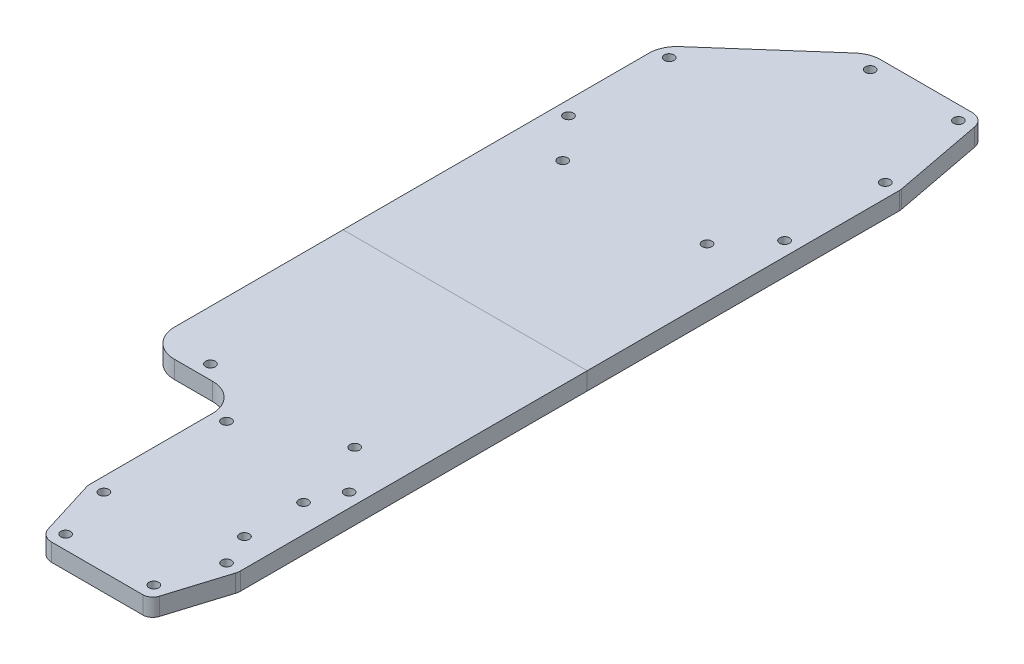
SolidWorks part; units mm, degrees
ref_plane "Front Plane" through (0, 0, 0) normal (0, 0, 1) x (1, 0, 0)
ref_plane "Top Plane" through (0, 0, 0) normal (0, 1, 0) x (1, 0, 0)
ref_plane "Right Plane" through (0, 0, 0) normal (1, 0, 0) x (0, 0, -1)
sketch "Sketch1" plane through (0, 0, 0) normal (0, 1, 0) x (1, 0, 0)
  line L0 (45, 295) -> (76.8, 295) construction
  line L1 (0, 0) -> (88, 0)
  line L2 (0, 0) -> (0, 300)
  line L3 (0, 300) -> (88, 300)
  line L4 (88, 0) -> (88, 300)
  line L5 (18, 211.2) -> (70, 211.2) construction
  line L6 (18, 211.2) -> (18, 84.2) construction
  line L7 (18, 84.2) -> (70, 84.2) construction
  line L8 (70, 211.2) -> (70, 84.2) construction
  line L9 (38.8, 69.2) -> (83, 69.2) construction
  line L10 (38.8, 69.2) -> (38.8, 25) construction
  line L11 (38.8, 25) -> (83, 25) construction
  line L12 (83, 69.2) -> (83, 25) construction
  line L13 (5.05, 226.2) -> (82.95, 226.2) construction
  line L14 (5.05, 226.2) -> (5.05, 262.5) construction
  line L15 (5.05, 262.5) -> (82.95, 262.5) construction
  line L16 (82.95, 226.2) -> (82.95, 262.5) construction
  line L17 (45, 5) -> (76.8, 5) construction
  line L18 (38.8, 25) -> (45, 5) construction
  line L19 (76.8, 5) -> (83, 25) construction
  line L20 (34.0242, 23.5195) -> (40.2242, 3.5195)
  line L21 (40, 300) -> (0, 264.7822)
  line L22 (87.7758, 23.5195) -> (81.2684, 2.5279)
  line L23 (78, 57.75) -> (78, 36.45) construction
  line L24 (5.05, 262.5) -> (0, 262.5) construction
  line L25 (5.05, 262.5) -> (1.7129, 266.2903) construction
  line L26 (78, 36.45) -> (83, 25) construction
  line L27 (78, 57.75) -> (83, 69.2) construction
  line L28 (81.7114, 295.9371) -> (87.9105, 263.4465)
  line L29 (33.8, 79.2) -> (0, 79.2)
  line L30 (33.8, 25) -> (33.8, 79.2)
  circle A0 centre (18, 211.2) radius 1.75
  circle A1 centre (70, 84.2) radius 1.75
  circle A2 centre (18, 84.2) radius 1.75
  circle A3 centre (70, 211.2) radius 1.75
  circle A4 centre (5.05, 262.5) radius 1.75
  circle A5 centre (5.05, 226.2) radius 1.75
  circle A6 centre (82.95, 226.2) radius 1.75
  circle A7 centre (82.95, 262.5) radius 1.75
  circle A8 centre (38.8, 69.2) radius 1.75
  circle A9 centre (83, 69.2) radius 1.75
  circle A10 centre (83, 25) radius 1.75
  circle A11 centre (38.8, 25) radius 1.75
  circle A12 centre (45, 295) radius 1.75
  circle A13 centre (76.8, 295) radius 1.75
  circle A14 centre (45, 5) radius 1.75
  circle A15 centre (76.8, 5) radius 1.75
  arc A16 (88, 25) -> (87.7758, 23.5195) centre (83, 25) cw
  arc A17 (77.8382, 0) -> (81.2684, 2.5279) centre (77.8382, 3.5912) ccw
  arc A18 (40.2242, 3.5195) -> (45, 0) centre (45, 5) ccw
  circle A19 centre (78, 57.75) radius 1.75
  circle A20 centre (78, 36.45) radius 1.75
  arc A21 (76.8, 300) -> (81.7114, 295.9371) centre (76.8, 295) cw
  arc A22 (87.9105, 263.4465) -> (88, 262.5) centre (82.95, 262.5) cw
  arc A23 (34.0242, 23.5195) -> (33.8, 25) centre (38.8, 25) cw
  point P61 (16.4478, 79.2)
  point P62 (34.0877, 79.2)
  dimension "D3" = 3.5
  dimension "D14" = 3.5
  dimension "D2" = 300
  dimension "D4" = 52
  dimension "D5" = 127
  dimension "D6" = 18
  dimension "D7" = 77.9
  dimension "D8" = 36.3
  dimension "D9" = 44.2
  dimension "D11" = 5.05
  dimension "D12" = 15
  dimension "D13" = 15
  dimension "D10" = 5
  dimension "D15" = 5
  dimension "D16" = 11.2
  dimension "D18" = 5
  dimension "D17" = 31.8
  dimension "D20" = 20
  dimension "D25" = 5
  dimension "D21" = 21.3
  dimension "D22" = 5
  dimension "D19" = 5
  dimension "D23" = 88
extrude "Boss-Extrude1" add sketch "Sketch1" along normal blind 6.35 contours L1 L4 L3 L2 A15 A14 A13 A12 A11 A10 A9 A8 A7 A6 A5 A4 A3 A2 A1 A0 region at (47.7069, 0, -159.2554)
fillet "Fillet1" radius 10 4 edges at (40, 3.175, -300) (0, 3.175, -264.7822) (0, 3.175, -79.2) (33.8, 3.175, -79.2)
ref_plane "Plane1" through (0, 0, -150) normal (0, 0, 1) x (1, 0, 0)
split "Split1" trim tools "Plane1" bodies to split 104 resulting bodies 105 106
equation "\"D13@Sketch1\"=\"D12@Sketch1\""
